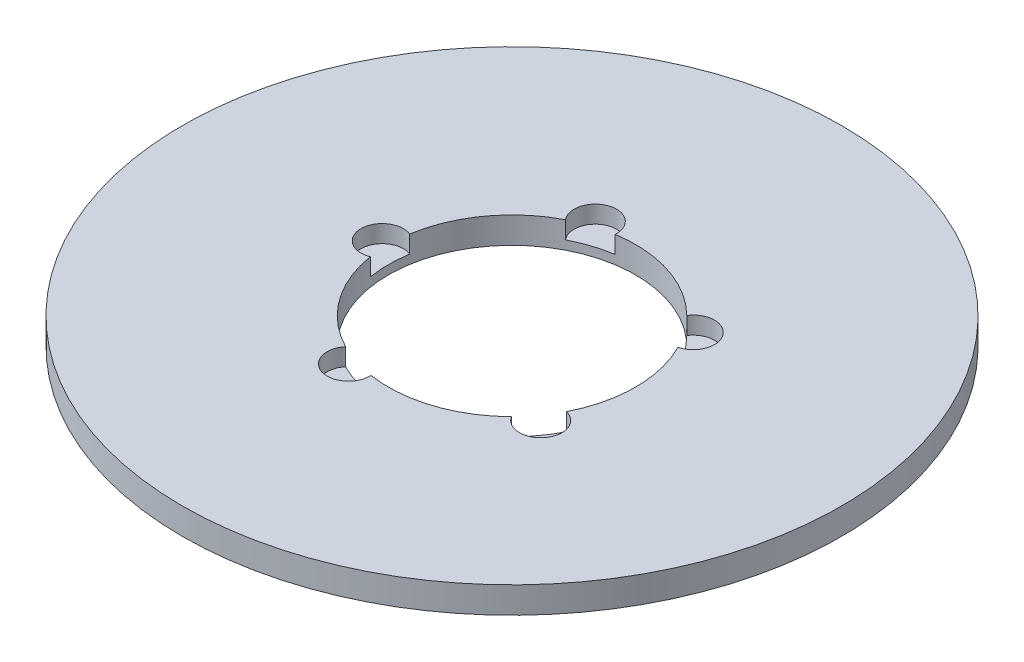
SolidWorks part; units mm, degrees
ref_plane "Front Plane" through (0, 0, 0) normal (0, 0, 1) x (1, 0, 0)
ref_plane "Top Plane" through (0, 0, 0) normal (0, 1, 0) x (1, 0, 0)
ref_plane "Right Plane" through (0, 0, 0) normal (1, 0, 0) x (0, 0, -1)
sketch "Sketch1" plane through (0, 0, 0) normal (0, 1, 0) x (1, 0, 0)
  circle A0 centre (0, 0) radius 100
  dimension "FLANGE_OD" = 200
extrude "Boss-Extrude1" add sketch "Sketch1" along normal blind 8
sketch "Sketch2" plane through (0, 0, 0) normal (0, 1, 0) x (1, 0, 0)
  circle A0 centre (0, 0) radius 37.5
  dimension "BORE_D" = 75
extrude "Cut-Extrude1" cut sketch "Sketch2" along normal through all
sketch "Sketch3" plane through (0, 8, 0) normal (0, 1, 0) x (1, 0, 0)
  circle A0 centre (0, 0) radius 39.3782 construction
  circle A1 centre (-39.3782, 0) radius 6.439
  dimension "BOLT_D" = 12.8781
  dimension "BOLT_PCD" = 78.7564
extrude "Cut-Extrude2" cut sketch "Sketch3" against normal blind 5.2872
pattern_circular "CirPattern1" count 5 over 360 about axis through (0, 0, 0) along (0, 1, 0) of "Cut-Extrude2"
